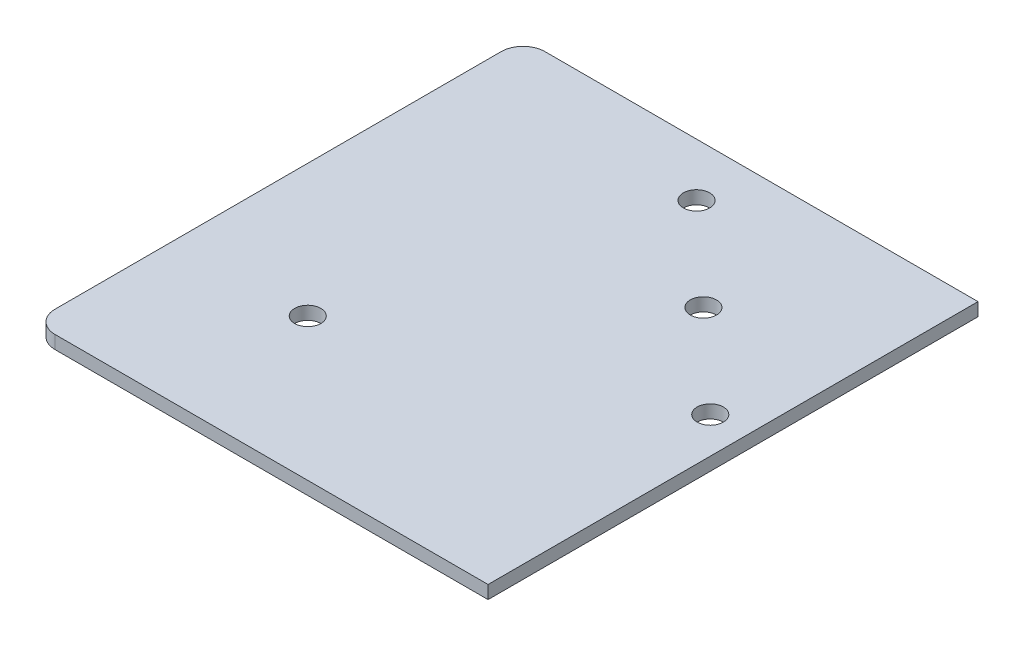
SolidWorks part; units mm, degrees
material "Oak"
ref_plane "Front Plane" through (0, 0, 0) normal (0, 0, 1) x (1, 0, 0)
ref_plane "Top Plane" through (0, 0, 0) normal (0, 1, 0) x (1, 0, 0)
ref_plane "Right Plane" through (0, 0, 0) normal (1, 0, 0) x (0, 0, -1)
sketch "Sketch1" plane through (0, 0, 0) normal (0, 1, 0) x (1, 0, 0)
  line L0 (558.8, 99.2707) -> (461.5124, 17.6367)
  line L1 (-558.8, -177.8) -> (558.8, -177.8)
  line L2 (-558.8, 177.8) -> (558.8, 177.8)
  line L3 (558.8, -177.8) -> (558.8, 177.8)
  line L4 (-558.8, -177.8) -> (558.8, 177.8) construction
  line L5 (-558.8, 177.8) -> (558.8, -177.8) construction
  line L6 (-228.6, 177.8) -> (228.6, 177.8)
  line L7 (-228.6, -177.8) -> (228.6, -177.8)
  line L8 (228.6, 177.8) -> (228.6, -177.8)
  line L9 (-228.6, 177.8) -> (228.6, -177.8) construction
  line L10 (-228.6, -177.8) -> (228.6, 177.8) construction
  line L11 (228.6, -177.8) -> (558.8, 99.2707)
  line L12 (-228.6, 177.8) -> (-228.6, -177.8)
  point P4 (0, 0)
extrude "Boss-Extrude1" add sketch "Sketch1" along normal blind 9.525 contours L8 L11 L0 L3 L2 region at (358.5765, 0, -54.5316)
extrude "Boss-Extrude2" add sketch "Sketch1<4>" along normal blind 9.525 contours L11 L1 L3 L0 region at (448.7333, 0, 85.4431)
sketch "Sketch1<4>" plane through (0, 0, 0) normal (0, 1, 0) x (1, 0, 0) same geometry as "Sketch1"
sketch "Sketch3" plane through (0, 0, 0) normal (0, -1, 0) x (1, 0, 0)
  line L0 (558.8, 177.8) -> (228.6, -177.8)
  line L1 (228.6, 177.8) -> (558.8, -177.8)
  line L2 (228.6, -177.8) -> (393.7, -177.8)
  line L3 (228.6, -177.8) -> (558.8, -177.8) construction
  line L4 (393.7, 0) -> (462.8338, -74.4518)
  line L5 (393.7, 0) -> (228.6, 0)
  line L6 (228.6, -177.8) -> (228.6, 177.8) construction
  line L7 (393.7, 0) -> (558.8, 0)
  line L8 (228.6, 0) -> (228.6, 177.8)
  line L9 (558.8, 177.8) -> (558.8, -177.8) construction
  line L10 (462.8338, -74.4518) -> (532.6324, -9.6389)
  line L11 (462.8338, -74.4518) -> (393.0353, -139.2648)
  circle A0 centre (462.8338, -74.4518) radius 9.525
  circle A2 centre (324.5662, 74.4518) radius 9.525
  circle A3 centre (532.6324, -9.6389) radius 9.525
  circle A4 centre (393.0353, -139.2648) radius 9.525
  dimension "D1" = 101.6
  dimension "D2" = 203.2
fillet "Fillet1" radius 15.875 2 edges at (228.6, 4.7625, 177.8) (228.6, 4.7625, -177.8)
extrude "Cut-Extrude2" cut sketch "Sketch3" against normal through all contours L1 A2 | L1 A2 | L10 A0 L4 | L4 A0 L11 | L1 A0 L10 | L11 A0 L1 | A3 | A4 region at (529.2493, 0, -1.0237) region at (401.6504, 0, -135.8817) region at (463.0454, 0, -68.7387) region at (457.1207, 0, -74.2402) region at (327.5285, 0, 77.2026) region at (321.6038, 0, 71.7011) region at (468.5469, 0, -74.6634) region at (462.6222, 0, -80.1649)
